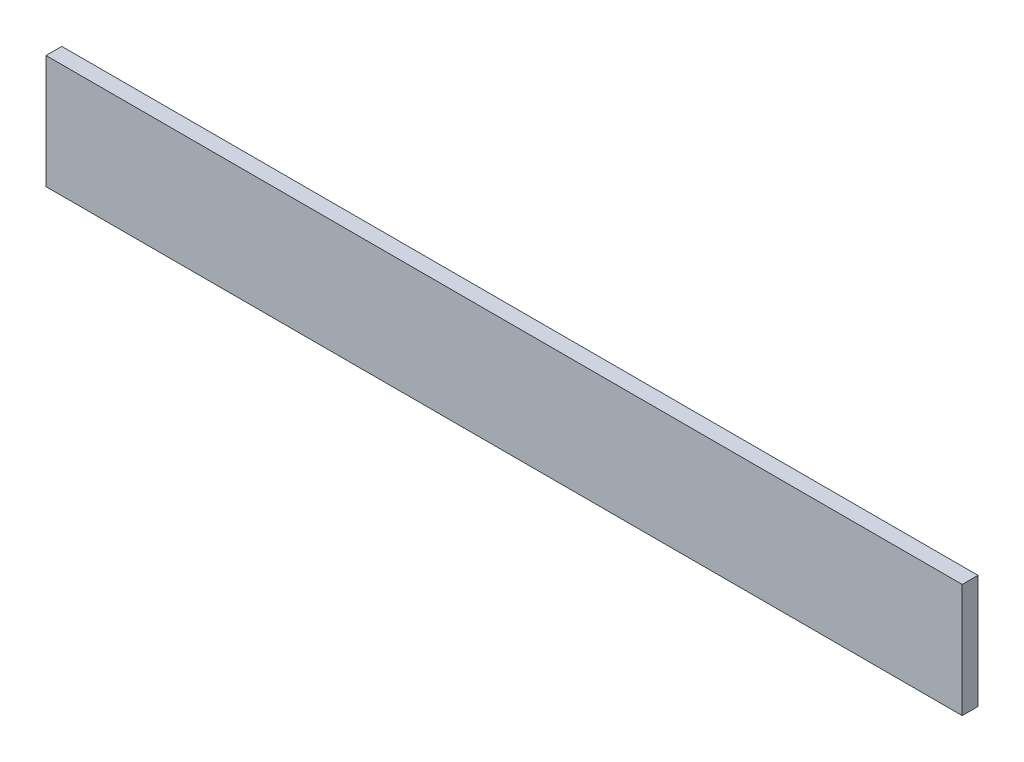
SolidWorks part; units mm, degrees
ref_plane "Plan de face" through (0, 0, 0) normal (0, 0, 1) x (1, 0, 0)
ref_plane "Plan de dessus" through (0, 0, 0) normal (0, 1, 0) x (1, 0, 0)
ref_plane "Plan de droite" through (0, 0, 0) normal (1, 0, 0) x (0, 0, -1)
sketch "Esquisse1" plane through (0, 0, 0) normal (0, 0, 1) x (1, 0, 0)
  line L1 (-142.6668, 70.5537) -> (234.3332, 70.5537)
  line L2 (-142.6668, 70.5537) -> (-142.6668, 23.8037)
  line L3 (-142.6668, 23.8037) -> (234.3332, 23.8037)
  line L4 (234.3332, 70.5537) -> (234.3332, 23.8037)
  dimension "D1" = 377
  dimension "D2" = 46.75
extrude "Boss.-Extru.1" add sketch "Esquisse1" along normal blind 6.5
